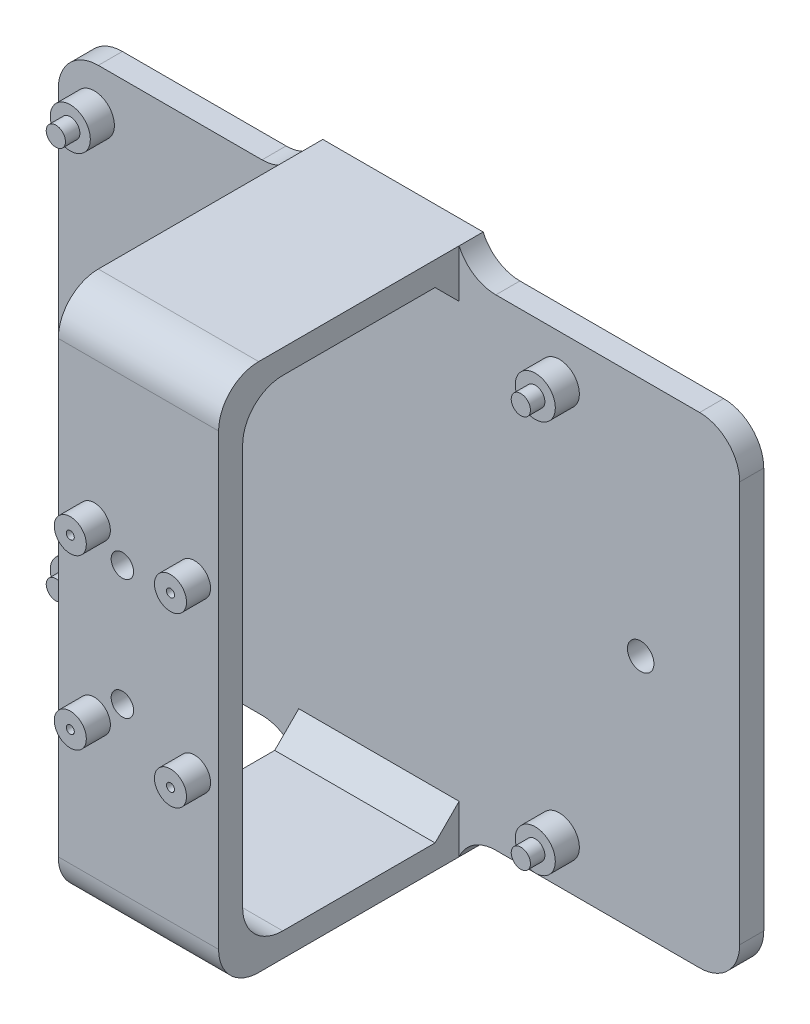
SolidWorks part; units mm, degrees
ref_plane "Front Plane" through (0, 0, 0) normal (0, 0, 1) x (1, 0, 0)
ref_plane "Top Plane" through (0, 0, 0) normal (0, 1, 0) x (1, 0, 0)
ref_plane "Right Plane" through (0, 0, 0) normal (1, 0, 0) x (0, 0, -1)
sketch "Sketch1" plane through (0, 0, 0) normal (0, 0, 1) x (1, 0, 0)
  line L1 (-42.5, 30) -> (42.5, 30)
  line L2 (-42.5, 30) -> (-42.5, -30)
  line L3 (-42.5, -30) -> (42.5, -30)
  line L4 (42.5, 30) -> (42.5, -30)
  line L5 (0, -30) -> (0, 30) construction
  line L6 (-42.5, 0) -> (42.5, 0) construction
  point P0 (0, 0)
  dimension "D1" = 60
  dimension "D2" = 85
extrude "Boss-Extrude1" add sketch "Sketch1" along normal blind 3
sketch "Sketch2" plane through (0, 0, 3) normal (0, 0, 1) x (1, 0, 0)
  line L0 (-42.5, 30) -> (-42.5, -30) construction
  line L1 (-38, 24.5) -> (20, 24.5) construction
  line L2 (-38, 24.5) -> (-38, -24.5) construction
  line L3 (-38, -24.5) -> (20, -24.5) construction
  line L4 (20, 24.5) -> (20, -24.5) construction
  circle A0 centre (-38, -24.5) radius 2.5
  circle A1 centre (-38, 24.5) radius 2.5
  circle A2 centre (20, 24.5) radius 2.5
  circle A3 centre (20, -24.5) radius 2.5
  point P4 (20, 0)
  dimension "D4" = 5
  dimension "D1" = 58
  dimension "D2" = 49
  dimension "D3" = 4.5
extrude "Boss-Extrude2" add sketch "Sketch2" along normal blind 3
sketch "Sketch3" plane through (0, 0, 6) normal (0, 0, 1) x (1, 0, 0)
  circle A0 centre (-38, 24.5) radius 1.2
  circle A1 centre (20, 24.5) radius 1.2
  circle A2 centre (-38, -24.5) radius 1.2
  circle A3 centre (20, -24.5) radius 1.2
  dimension "D1" = 2.4
extrude "Boss-Extrude3" add sketch "Sketch3" along normal blind 1.8
sketch "Sketch5" plane through (0, -30, 0) normal (0, -1, 0) x (1, 0, 0)
  line L0 (-42.5, 0) -> (42.5, 0) construction
  line L1 (-12.5, 0) -> (7.5, 0)
  line L2 (-12.5, 0) -> (-12.5, 30)
  line L3 (-12.5, 30) -> (7.5, 30)
  line L4 (7.5, 0) -> (7.5, 30)
  line L5 (-42.5, 3) -> (-42.5, 0) construction
  dimension "D1" = 20
  dimension "D2" = 30
  dimension "D3" = 30
extrude "Boss-Extrude4" add sketch "Sketch5" along normal blind 3
mirror "Mirror1" about plane through (0, 0, 0) normal (0, 1, 0) of "Boss-Extrude4"
sketch "Sketch6" plane through (0, 0, 30) normal (0, 0, 1) x (1, 0, 0)
  line L1 (-12.5, 33) -> (7.5, 33)
  line L2 (-12.5, 33) -> (-12.5, -33)
  line L3 (-12.5, -33) -> (7.5, -33)
  line L4 (7.5, 33) -> (7.5, -33)
extrude "Boss-Extrude5" add sketch "Sketch6" along normal blind 3
sketch "Sketch7" plane through (0, 0, 33) normal (0, 0, 1) x (1, 0, 0)
  line L0 (7.5, -33) -> (7.5, 33) construction
  line L1 (-8, 10.5) -> (4.5, 10.5) construction
  line L2 (-8, 10.5) -> (-8, -10.5) construction
  line L3 (-8, -10.5) -> (4.5, -10.5) construction
  line L4 (4.5, 10.5) -> (4.5, -10.5) construction
  circle A0 centre (-8, -10.5) radius 2
  circle A1 centre (4.5, -10.5) radius 2
  circle A2 centre (-8, 10.5) radius 2
  circle A3 centre (4.5, 10.5) radius 2
  point P4 (4.5, 0)
  dimension "D4" = 4
  dimension "D1" = 12.5
  dimension "D2" = 21
  dimension "D3" = 3
extrude "Boss-Extrude6" add sketch "Sketch7" along normal blind 3
sketch "Sketch8" plane through (0, 0, 36) normal (0, 0, 1) x (1, 0, 0)
  circle A0 centre (-8, 10.5) radius 0.5
  circle A1 centre (4.5, 10.5) radius 0.5
  circle A2 centre (-8, -10.5) radius 0.5
  circle A3 centre (4.5, -10.5) radius 0.5
  dimension "D1" = 1
extrude "Cut-Extrude2" cut sketch "Sketch8" against normal blind 5
sketch "Sketch9" plane through (0, 0, 3) normal (0, 0, 1) x (1, 0, 0)
  line L0 (0, 0) -> (0, 16.6013) construction
  circle A0 centre (-30.15, 0) radius 1.65
  circle A1 centre (30.15, 0) radius 1.65
  point P7 (0, 0)
  dimension "D1" = 60.3
  dimension "D2" = 3.3
extrude "Cut-Extrude3" cut sketch "Sketch9" against normal blind 3
fillet "Fillet1" radius 5 12 edges at (7.5, -30, 1.5) (-12.5, -30, 1.5) (-12.5, 30, 1.5) (7.5, 30, 1.5) (42.5, 30, 1.5) (42.5, -30, 1.5) (-42.5, 30, 1.5) (-42.5, -30, 1.5) (-2.5, -33, 33) (-2.5, 33, 33) (-2.5, -30, 30) (-2.5, 30, 30)
chamfer "Chamfer1" distance 3 angle 45 2 edges at (-2.5, 30, 3) (-2.5, -30, 3)
sketch "Sketch10" plane through (0, 0, 30) normal (0, 0, -1) x (-1, 0, 0)
  line L0 (12.5, 28) -> (12.5, -28) construction
  circle A0 centre (4.5, -7.5) radius 1.4
  circle A1 centre (4.5, 7.5) radius 1.4
  point P7 (0, 0)
  dimension "D1" = 2.8
  dimension "D2" = 15
  dimension "D3" = 7.5
  dimension "D4" = 8
extrude "Cut-Extrude4" cut sketch "Sketch10" against normal blind 3
